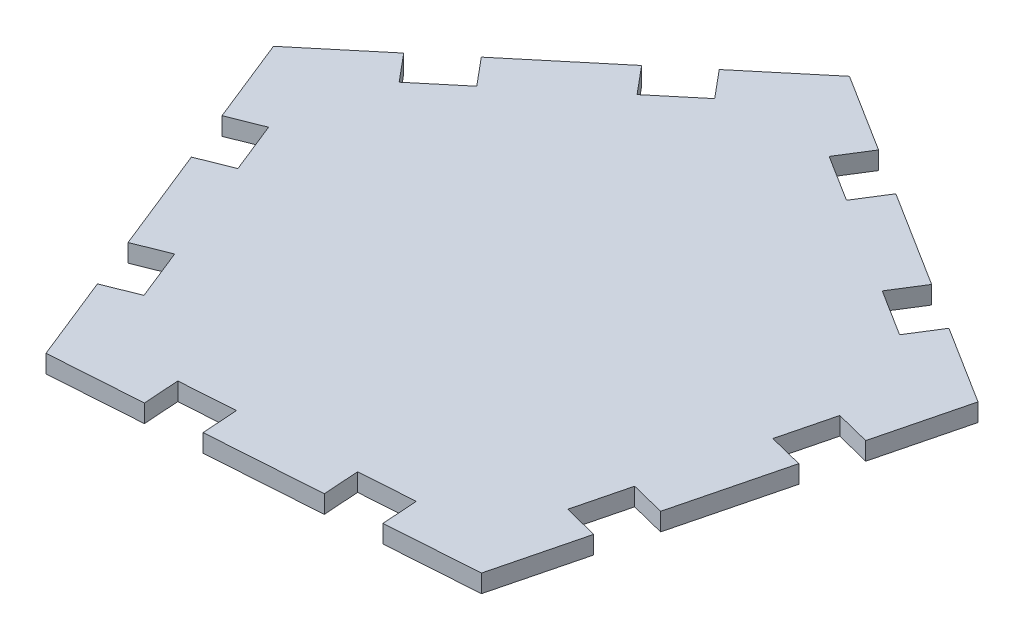
SolidWorks part; units mm, degrees
ref_plane "Front Plane" through (0, 0, 0) normal (0, 0, 1) x (1, 0, 0)
ref_plane "Top Plane" through (0, 0, 0) normal (0, 1, 0) x (1, 0, 0)
ref_plane "Right Plane" through (0, 0, 0) normal (1, 0, 0) x (0, 0, -1)
sketch "Sketch1" plane through (0, 0, 0) normal (0, 1, 0) x (1, 0, 0)
  line L1 (-59.9258, 15.1181) -> (-32.8962, -52.3211)
  line L2 (-32.8962, -52.3211) -> (39.5948, -47.4543)
  line L3 (39.5948, -47.4543) -> (57.3672, 22.9927)
  line L4 (57.3672, 22.9927) -> (-4.14, 61.6646)
  line L5 (-4.14, 61.6646) -> (-59.9258, 15.1181)
  circle A0 centre (0, 0) radius 50 construction
  dimension "D1" = 100
extrude "Boss-Extrude1" add sketch "Sketch1" along normal blind 3.18
ref_axis "Axis" through (0, 3.339, 0) along (0, -1, 0)
sketch "Axis Check" [suppressed] plane through (0, 3.18, 0) normal (0, 1, 0) x (1, 0, 0)
  line L0 (3.3493, -49.8877) -> (-4.14, 61.6646) construction
  line L1 (-32.8962, -52.3211) -> (39.5948, -47.4543) construction
  line L2 (57.3672, 22.9927) -> (-46.411, -18.6015) construction
  line L3 (-59.9258, 15.1181) -> (-32.8962, -52.3211) construction
  line L4 (-32.0329, 38.3913) -> (39.5948, -47.4543) construction
  line L5 (-4.14, 61.6646) -> (-59.9258, 15.1181) construction
  line L6 (-59.9258, 15.1181) -> (48.481, -12.2308) construction
  line L7 (39.5948, -47.4543) -> (57.3672, 22.9927) construction
  line L8 (-32.8962, -52.3211) -> (26.6136, 42.3287) construction
  line L9 (57.3672, 22.9927) -> (-4.14, 61.6646) construction
sketch "Sketch2" plane through (0, 0, 0) normal (0, -1, 0) x (1, 0, 0)
  line L0 (-53.8144, 0.1299) -> (-47.9109, -2.2362)
  line L1 (-53.8144, 0.1299) -> (-50.1723, 9.2172)
  line L2 (-47.9109, -2.2362) -> (-44.2688, 6.8511)
  line L3 (-50.1723, 9.2172) -> (-44.2688, 6.8511)
  line L4 (-59.9258, -15.1181) -> (-32.8962, 52.3211) construction
  line L5 (-42.6498, 27.9858) -> (-39.0076, 37.0731)
  line L6 (-42.6498, 27.9858) -> (-36.7463, 25.6197)
  line L7 (-39.0076, 37.0731) -> (-33.1041, 34.707)
  line L8 (-36.7463, 25.6197) -> (-33.1041, 34.707)
  line L9 (-46.411, 18.6015) -> (-19.2439, 7.7129) construction
  line L10 (-40.8287, 32.5295) -> (-34.9252, 30.1634) construction
  dimension "D1" = 6.36
  dimension "D3" = 10.11
  dimension "D2" = 9.79
extrude "Cut F" cut sketch "Sketch2" against normal through all
sketch "Sketch4" [suppressed] plane through (0, 3.18, 0) normal (0, 1, 0) x (1, 0, 0)
  line L9 (26.6136, 42.3287) -> (-26.6136, -42.3287) construction
  line L10 (57.3672, 22.9927) -> (-4.14, 61.6646) construction
  line L11 (-34.4964, -17.2915) -> (0.6335, 38.5824)
  line L12 (-34.4964, -17.2915) -> (-0.6335, -38.5824)
  line L13 (0.6335, 38.5824) -> (34.4964, 17.2915)
  line L14 (-0.6335, -38.5824) -> (34.4964, 17.2915)
  line L15 (-34.4964, -17.2915) -> (34.4964, 17.2915) construction
  line L16 (0.6335, 38.5824) -> (-0.6335, -38.5824) construction
  line L20 (0, 0) -> (39.0006, -24.5211) construction
  circle A0 centre (-21.8232, -34.7095) radius 3.25
  circle A1 centre (23.7041, -14.9036) radius 3.25
  point P5 (0, 0)
  point P6 (-21.8232, -34.7095)
  dimension "D3" = 6.5
  dimension "D1" = 40
  dimension "D2" = 66
  dimension "D4" = 8
  dimension "D5" = 8
extrude "Top Cut" [suppressed] cut sketch "Sketch4" against normal blind 10
sketch "Sketch7" [suppressed] plane through (0, 3.18, 0) normal (0, 1, 0) x (1, 0, 0)
  line L0 (0, 0) -> (26.6136, 42.3287) construction
  line L1 (57.3672, 22.9927) -> (-4.14, 61.6646) construction
  line L2 (-7.1857, -11.4287) -> (-30.8897, 3.4749) construction
  line L3 (-14.3588, -11.6437) -> (-33.0188, 0.0886) construction
  line L5 (0.6335, 38.5824) -> (-34.4964, -17.2915) construction
  circle A0 centre (-30.8897, 3.4749) radius 1
  circle A1 centre (-33.0188, 0.0886) radius 1
  dimension "D5" = 2
  dimension "D1" = 4
  dimension "D2" = 17.5
  dimension "D3" = 8
  dimension "D4" = 8
extrude "Top Cut 2" [suppressed] cut sketch "Sketch7" against normal through all
sketch "Sketch10" [suppressed] plane through (0, 3.18, 0) normal (0, 1, 0) x (1, 0, 0)
  line L0 (26.6136, 42.3287) -> (17.565, 27.9369) construction
  line L1 (57.3672, 22.9927) -> (-4.14, 61.6646) construction
  line L2 (34.4964, 17.2915) -> (0.6335, 38.5824) construction
  line L3 (33.0578, 31.7802) -> (13.6147, 44.0048) construction
  line L4 (34.4964, 17.2915) -> (0.6335, 38.5824) construction
  circle A0 centre (19.4532, 40.3339) radius 1
  circle A1 centre (27.919, 35.0111) radius 1
  dimension "D1" = 11.5
  dimension "D2" = 2
  dimension "D3" = 5
extrude "Top Cut 3" [suppressed] cut sketch "Sketch10" against normal blind 10
sketch "Sketch8" [suppressed] plane through (0, 3.18, 0) normal (0, 1, 0) x (1, 0, 0)
  line L0 (3.3493, -49.8877) -> (-4.14, 61.6646) construction
  line L5 (-32.8962, -52.3211) -> (39.5948, -47.4543) construction
  line L6 (-17.9455, -31.2723) -> (21.9647, -28.5929)
  line L11 (-17.9455, -31.2723) -> (-21.9647, 28.5929)
  line L12 (21.9647, -28.5929) -> (17.9455, 31.2723)
  line L13 (-21.9647, 28.5929) -> (17.9455, 31.2723)
  point P4 (1.4955, -22.2759)
  dimension "D1" = 60
  dimension "D2" = 40
  dimension "D3" = 20
extrude "Bottom Cut" [suppressed] cut sketch "Sketch8" against normal blind 10
sketch "Sketch9" [suppressed] plane through (0, 3.18, 0) normal (0, 1, 0) x (1, 0, 0)
  line L0 (19.9551, 1.3397) -> (-19.9551, -1.3397) construction
  line L1 (21.9647, -28.5929) -> (17.9455, 31.2723) construction
  line L2 (-21.9647, 28.5929) -> (-17.9455, -31.2723) construction
  line L3 (-19.9551, -1.3397) -> (-44.4689, -2.9855) construction
  line L4 (19.9551, 1.3397) -> (42.6839, 2.8657) construction
  line L5 (-32.8962, -52.3211) -> (39.5948, -47.4543) construction
  line L6 (-29.6051, -6.8886) -> (-32.3788, -7.0748)
  line L7 (-29.6051, -6.8886) -> (-30.2602, 2.8694)
  line L8 (-30.2602, 2.8694) -> (-33.0339, 2.6832)
  line L9 (-32.3788, -7.0748) -> (-33.0339, 2.6832)
  line L10 (-29.6051, -6.8886) -> (-33.0339, 2.6832) construction
  line L11 (-30.2602, 2.8694) -> (-32.3788, -7.0748) construction
  line L12 (33.0339, -2.6832) -> (30.2602, -2.8694)
  line L13 (33.0339, -2.6832) -> (32.3788, 7.0748)
  line L14 (32.3788, 7.0748) -> (29.6051, 6.8886)
  line L15 (30.2602, -2.8694) -> (29.6051, 6.8886)
  line L16 (33.0339, -2.6832) -> (29.6051, 6.8886) construction
  line L17 (32.3788, 7.0748) -> (30.2602, -2.8694) construction
  line L18 (-32.8962, -52.3211) -> (39.5948, -47.4543) construction
  point P6 (-31.3195, -2.1027)
  point P13 (31.3195, 2.1027)
  dimension "D1" = 9.79
  dimension "D4" = 9.79
  dimension "D5" = 10
  dimension "D6" = 10
  dimension "D2" = 2.78
  dimension "D3" = 2.78
extrude "Battery Holder Cut" [suppressed] cut sketch "Sketch9" against normal blind 6.36
sketch "Sketch3" [suppressed] plane through (0, 3.18, 0) normal (0, 1, 0) x (1, 0, 0)
  line L0 (0, 0) -> (-40.9819, 49.1167) construction
  line L1 (-51.5408, 30.3975) -> (-43.3916, 20.6307)
  line L3 (-43.3916, 20.6307) -> (-35.5521, 27.1718)
  line L4 (-43.7013, 36.9386) -> (-35.5521, 27.1718)
  line L5 (-4.14, 61.6646) -> (-59.9258, 15.1181) construction
  line L6 (-71.9961, 5.0469) -> (-69.9588, 2.6052)
  line L7 (-71.9961, 5.0469) -> (-47.4739, 25.5077)
  line L14 (-28.5137, 49.6108) -> (-20.3645, 39.8441)
  line L16 (-20.3645, 39.8441) -> (-12.525, 46.3852)
  line L17 (-20.6742, 56.1519) -> (-12.525, 46.3852)
  line L18 (-40.4979, 25.131) -> (-39.4719, 23.9013) construction
  line L19 (-51.5408, 30.3975) -> (-43.7013, 36.9386)
  line L21 (-28.5137, 49.6108) -> (-20.6742, 56.1519)
  line L22 (-16.5996, 51.2685) -> (4.7866, 69.1127)
  line L23 (-39.6267, 32.0552) -> (-24.4391, 44.7274)
  line M18 (-4.14, 61.6646) -> (-59.9258, 15.1181)
  dimension "D1" = 12.72
  dimension "D2" = 10.21
  dimension "D3" = 9.89
  dimension "D4" = 100
extrude "Extrude M" [suppressed] add sketch "Sketch3" against normal up to surface (3.18 mm away) contours L21 L14 L7 L17 | L19 L1 L4 M18 up to face at (-26.7442, 0, 10.7191)
pattern_circular "Circle F" count 5 over 360 about axis through (0, 3.339, 0) along (0, -1, 0) of "Cut F"
pattern_circular "Circle M" [suppressed] count 5 over 360 about axis through (0, 3.339, 0) along (0, -1, 0) of bodies 173
pattern_circular "Circle Side F" [suppressed] count 5 over 360 about axis through (0, 3.339, 0) along (0, -1, 0) of bodies 173
pattern_circular "Circle Side M" [suppressed] count 5 over 360 about axis through (0, 3.339, 0) along (0, -1, 0) of bodies 168
equation "\"kerf\" = .21mm"
equation "\"tabWidthF\"= 10 - \"kerf\""
equation "\"tabThickness\" = 6.36mm"
equation "\"D1@Sketch2\"=\"tabThickness\""
equation "\"tabWidthM\"= 10 + \"kerf\""
equation "\"halfkerf\"= \"kerf\" / 2.00mm"
equation "\"D1@Sketch9\"=\"tabWidthF\""
equation "\"D4@Sketch9\"=\"tabWidthF\""
equation "\"D1@Battery Holder Cut\" = \"tabThickness\""
equation "\"tabLength\" = \"kerf\" + 12"
